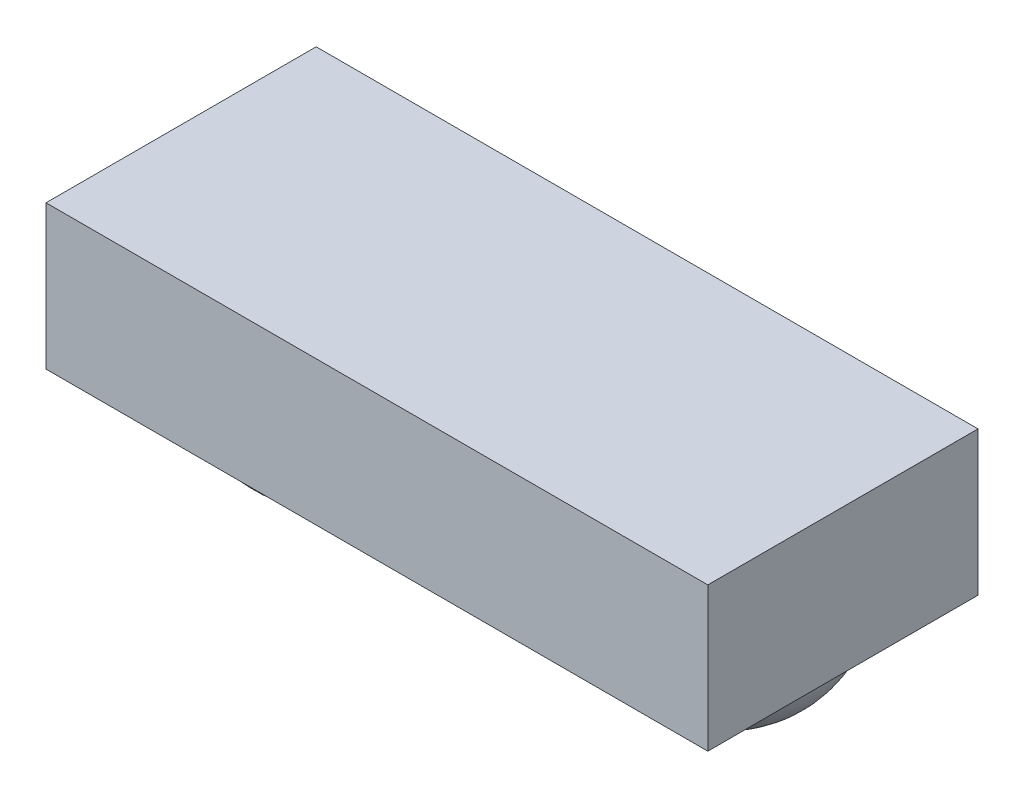
SolidWorks part; units mm, degrees
ref_plane "Front Plane" through (0, 0, 0) normal (0, 0, 1) x (1, 0, 0)
ref_plane "Top Plane" through (0, 0, 0) normal (0, 1, 0) x (1, 0, 0)
ref_plane "Right Plane" through (0, 0, 0) normal (1, 0, 0) x (0, 0, -1)
sketch "Sketch1" plane through (0, 0, 0) normal (0, 0, 1) x (1, 0, 0)
  line L1 (4.985, 3.5904) -> (-4.985, 3.5904)
  line L2 (4.985, 3.5904) -> (4.985, 1.4204)
  line L3 (4.985, 1.4204) -> (-4.985, 1.4204)
  line L4 (-4.985, 3.5904) -> (-4.985, 1.4204)
  line L5 (0, 1.4204) -> (0, 3.5904) construction
  line L6 (4.985, 2.5054) -> (-4.985, 2.5054) construction
  line L7 (-0.875, 0.7904) -> (0.875, 0.7904)
  line L8 (-0.875, 0.7904) -> (-0.875, 1.4204)
  line L9 (-0.875, 1.4204) -> (0.875, 1.4204)
  line L10 (0.875, 0.7904) -> (0.875, 1.4204)
  line L11 (0, 1.4204) -> (0, 0.7904) construction
  line L12 (-0.875, 1.1054) -> (0.875, 1.1054) construction
  arc A0 (-1.405, 1.4204) -> (-4.605, 1.4204) centre (-3.005, 1.4204) cw construction
  arc A1 (1.505, 1.4204) -> (4.705, 1.4204) centre (3.105, 1.4204) ccw construction
  point P0 (0, 2.5054)
  point P4 (0, 1.1054)
  dimension "D6" = 1.6
  dimension "D1" = 2.17
  dimension "D2" = 9.97
  dimension "D3" = 2.8
  dimension "D4" = 1.88
  dimension "D5" = 1.98
  dimension "D7" = 1.75
extrude "Boss-Extrude1" add sketch "Sketch1" along normal blind 4.07 contours L1 L4 L3 L2 region at (0, 2.5054, 0)
extrude "Boss-Extrude2" add sketch "Sketch1<3>" along normal blind 0.2 contours L7 L10 L3 L8 region at (0, 1.1054, 0)
sketch "Sketch1<3>" plane through (0, 0, 0) normal (0, 0, 1) x (1, 0, 0) same geometry as "Sketch1"
ref_plane "Plane1" through (0, 0, 1.78) normal (0, 0, 1) x (1, 0, 0)
sketch "Sketch2" plane through (0, 0, 1.78) normal (0, 0, 1) x (1, 0, 0)
  line L0 (-4.605, 1.4204) -> (-4.605, 1.3804)
  line L1 (4.985, 1.4204) -> (-4.985, 1.4204) construction
  line L2 (-1.405, 1.4204) -> (-1.405, 1.3804)
  line L3 (-4.985, 3.5904) -> (-4.985, 1.4204) construction
  line L4 (4.985, 3.5904) -> (-4.985, 3.5904) construction
  line L5 (-3.005, 1.4204) -> (-3.005, -0.2196)
  line L6 (-4.605, 1.4204) -> (-1.405, 1.4204)
  arc A0 (-4.605, 1.3804) -> (-1.405, 1.3804) centre (-3.005, 1.3804) ccw
  dimension "D2" = 1.6
  dimension "D3" = 3.81
  dimension "D1" = 1.98
revolve "Revolve1" add sketch "Sketch2" angle 360 about L5 region at (-3.6878, 0.7229, 1.78)
ref_plane "Plane2" through (0, 0, 1.9) normal (0, 0, 1) x (1, 0, 0)
sketch "Sketch3" plane through (0, 0, 1.9) normal (0, 0, 1) x (1, 0, 0)
  line L1 (1.505, 1.6204) -> (4.705, 1.6204)
  line L2 (4.985, 3.5904) -> (-4.985, 3.5904) construction
  line L3 (4.985, 3.5904) -> (4.985, 1.4204) construction
  line L4 (3.105, 1.6204) -> (3.105, 0.0204)
  arc A0 (1.505, 1.6204) -> (4.705, 1.6204) centre (3.105, 1.6204) ccw
  dimension "D1" = 1.6
  dimension "D2" = 3.57
  dimension "D3" = 1.88
revolve "Revolve2" add sketch "Sketch3" angle 360 about L4 region at (2.4259, 0.9414, 1.9)
